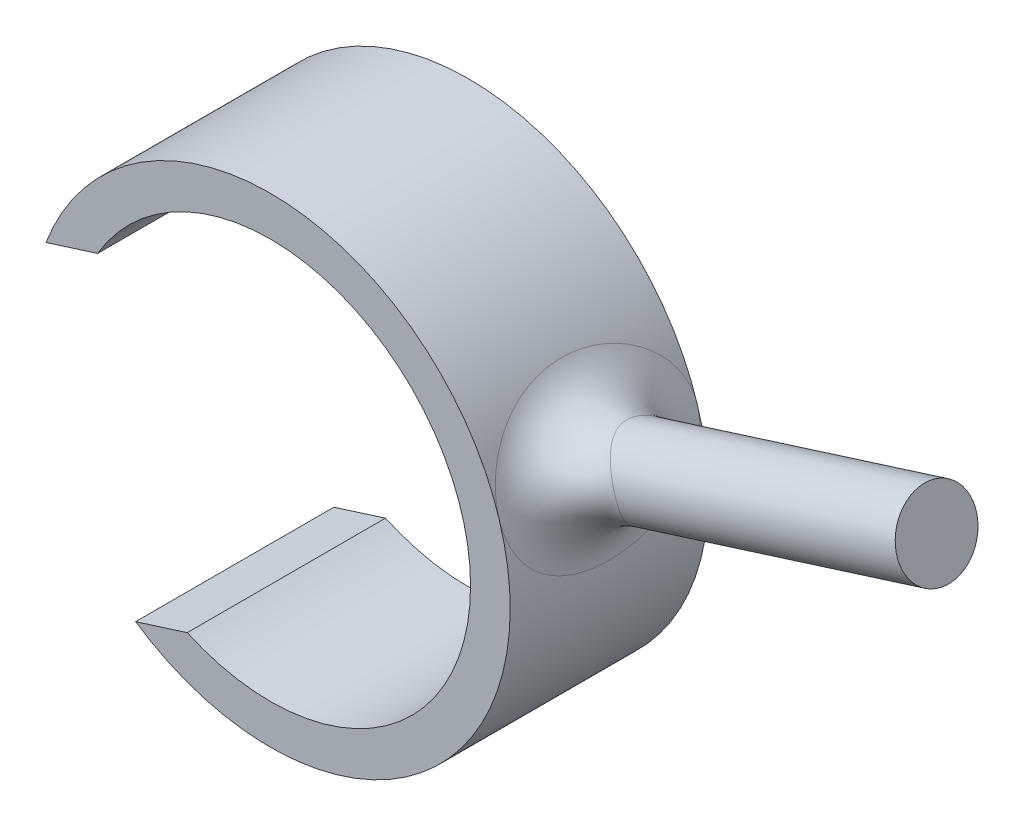
SolidWorks part; units mm, degrees
ref_plane "前视基准面" through (0, 0, 0) normal (0, 0, 1) x (1, 0, 0)
ref_plane "上视基准面" through (0, 0, 0) normal (0, 1, 0) x (1, 0, 0)
ref_plane "右视基准面" through (0, 0, 0) normal (1, 0, 0) x (0, 0, -1)
other "Configuration Table"
sketch "草图1" plane through (0, 0, 0) normal (0, 0, 1) x (1, 0, 0)
  circle A0 centre (0, 0) radius 10.1
  circle A1 centre (0, 0) radius 12.1
  dimension "D1" = 20.2
  dimension "D2" = 24.2
extrude "凸台-拉伸1" add sketch "草图1" along normal blind 10
ref_plane "基准面1" through (17.1637, 5.4228, 0) normal (-0.9535, -0.3013, 0) x (0, 0, 1)
sketch "草图2" plane through (17.1637, 5.4228, 0) normal (-0.9535, -0.3013, 0) x (0, 0, 1)
  circle A0 centre (5, 0) radius 2
extrude "凸台-拉伸2" add sketch "草图2" along normal up to next and the other way blind 3
sketch "草图4" plane through (20.0243, 6.3266, 0) normal (0.9535, 0.3013, 0) x (0, 0, -1)
  circle A1 centre (-5, 0) radius 2
  circle A2 centre (-5, 0) radius 2
  dimension "D1" = 0
extrude "凸台-拉伸3" add sketch "草图4" along normal blind 9
sketch "草图3" plane through (0, 0, 0) normal (0, 1, 0) x (1, 0, 0)
  line L0 (0, 0) -> (0, -5) construction
  line L1 (12.1, 0) -> (-12.1, 0) construction
  line L2 (10.1, 0) -> (-10.1, 0) construction
  line L3 (0, -5) -> (0, -18.0924)
  line L4 (0, -18.0924) -> (0, 0)
  line L5 (0, 6.2699) -> (0, 8.0924)
  line L6 (-12.1, -10) -> (12.1, -10) construction
  line L7 (-12.1, -10) -> (12.1, -10)
  line L8 (12.1, 0) -> (-12.1, 0)
  arc A0 (0, 8.0924) -> (0, -18.0924) centre (0, -5) ccw
  arc A1 (0, 6.2699) -> (0, -16.2699) centre (0, -5) ccw
  dimension "D1" = 5
sketch "草图5" plane through (0, 0, 0) normal (0, 0, -1) x (-1, 0, 0)
  line L0 (8.7098, 5.1136) -> (4.1908, -9.1895)
  line L1 (4.1908, -9.1895) -> (9.2783, -10.7969)
  line L2 (9.2783, -10.7969) -> (13.7973, 3.5062)
  line L3 (-28.0037, 10.9451) -> (-29.2087, 7.1309) construction
  line L4 (13.7973, 3.5062) -> (8.7098, 5.1136)
  circle A0 centre (0, 0) radius 10.1 construction
  circle A1 centre (0, 0) radius 12.1 construction
  dimension "D1" = 15
extrude "切除-拉伸1" cut sketch "草图5" against normal blind 10
fillet "圆角1" radius 3 1 edges at (11.975, 1.7349, 5.4296)
